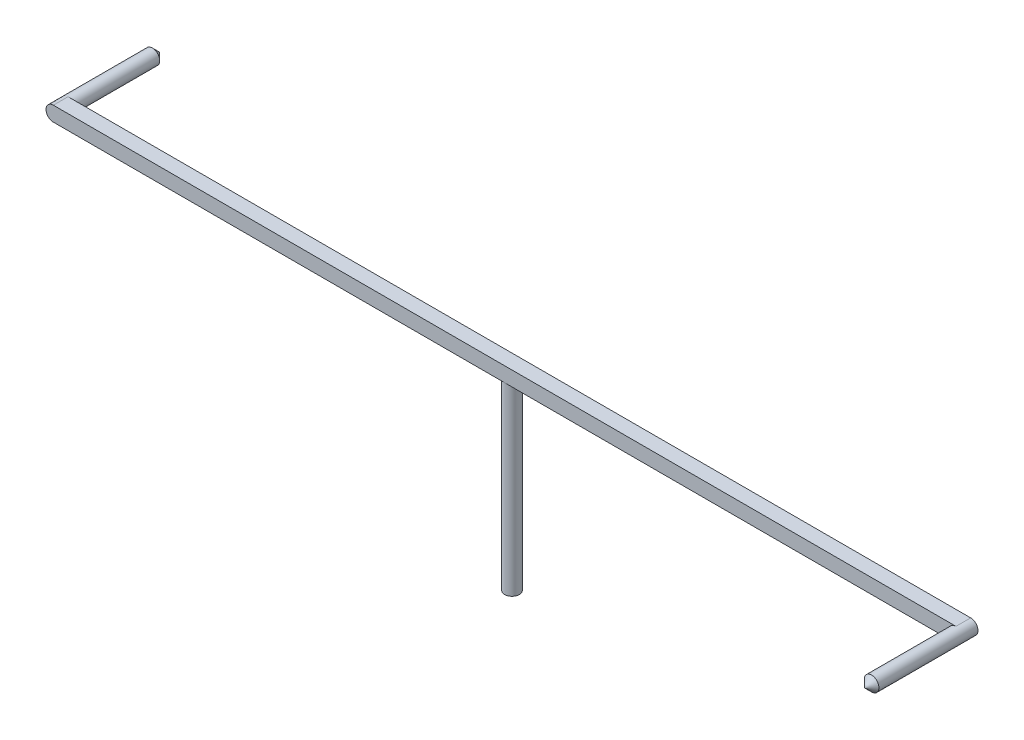
SolidWorks part; units mm, degrees
ref_plane "前视基准面" through (0, 0, 0) normal (0, 0, 1) x (1, 0, 0)
ref_plane "上视基准面" through (0, 0, 0) normal (0, 1, 0) x (1, 0, 0)
ref_plane "右视基准面" through (0, 0, 0) normal (1, 0, 0) x (0, 0, -1)
sketch "草图1" plane through (0, 0, 0) normal (0, 1, 0) x (1, 0, 0)
  circle A0 centre (0, 0) radius 0.4
  dimension "D1" = 0.8
extrude "凸台-拉伸1" add sketch "草图1" along normal blind 10
sketch "草图2" plane through (0, 10, 0) normal (0, 1, 0) x (1, 0, 0)
  line L1 (-25, 0.4) -> (25, 0.4)
  line L2 (-25, 0.4) -> (-25, -0.4)
  line L3 (-25, -0.4) -> (25, -0.4)
  line L4 (25, 0.4) -> (25, -0.4)
  circle A0 centre (0, 0) radius 0.4 construction
  dimension "D1" = 25
  dimension "D2" = 25
extrude "凸台-拉伸2" add sketch "草图2" along normal blind 0.8
fillet "圆角1" radius 0.4 4 edges at (25, 10, 0) (25, 10.8, 0) (-25, 10, 0) (-25, 10.8, 0)
sketch "草图3" plane through (0, 0, 0.4) normal (0, 0, 1) x (1, 0, 0)
  circle A0 centre (24.6, 10.4) radius 0.4
  dimension "D1" = 0.8
extrude "凸台-拉伸3" add sketch "草图3" along normal blind 5
sketch "草图4" plane through (0, 0, -0.4) normal (0, 0, -1) x (-1, 0, 0)
  circle A0 centre (24.6, 10.4) radius 0.4
  dimension "D1" = 0.8
extrude "凸台-拉伸4" add sketch "草图4" along normal blind 5
chamfer "倒角1" distance 0.4 angle 45 2 edges at (-25, 10.4, -5.4) (25, 10.4, 5.4)
